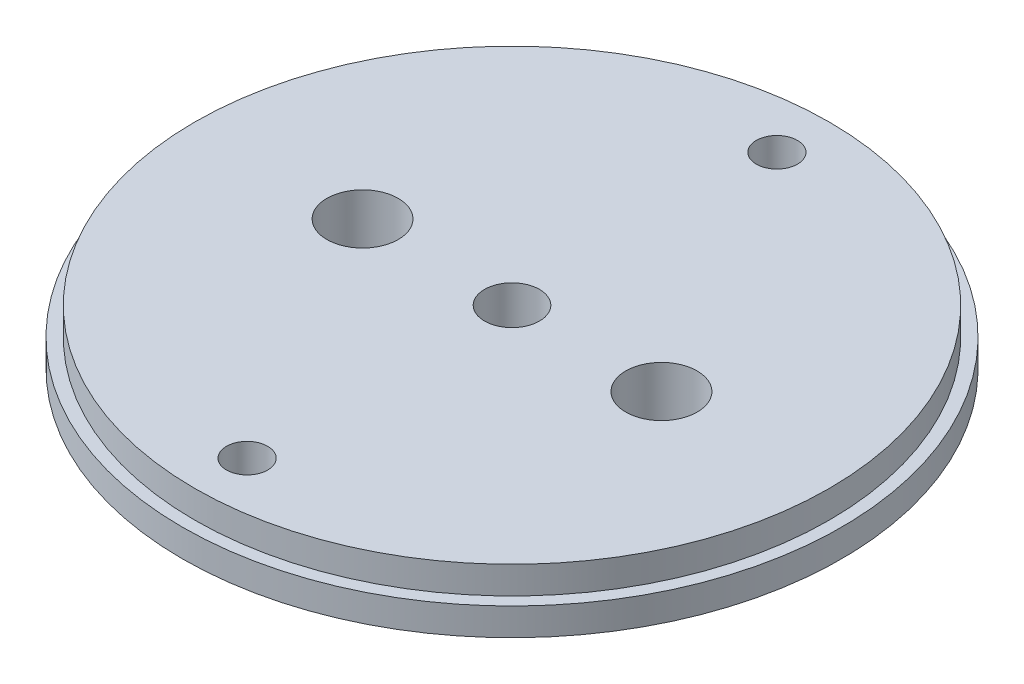
SolidWorks part; units mm, degrees
ref_plane "Front Plane" through (0, 0, 0) normal (0, 0, 1) x (1, 0, 0)
ref_plane "Top Plane" through (0, 0, 0) normal (0, 1, 0) x (1, 0, 0)
ref_plane "Right Plane" through (0, 0, 0) normal (1, 0, 0) x (0, 0, -1)
sketch "Sketch1" plane through (0, 0, 0) normal (0, 1, 0) x (1, 0, 0)
  circle A0 centre (0, 0) radius 73.3425
  circle A1 centre (0, 0) radius 76.1746
  dimension "D1" = 146.685
  dimension "D2" = 152.3492
extrude "Boss-Extrude1" add sketch "Sketch1" along normal blind 6.35 contours A0 | A1 A0 region at (0, 0, 0) region at (-74.0201, 0, 0)
extrude "Boss-Extrude2" add sketch "Sketch1<3>" along normal blind 12.7 contours A0 region at (0, 0, 0)
sketch "Sketch1<3>" plane through (0, 0, 0) normal (0, 1, 0) x (1, 0, 0) same geometry as "Sketch1"
sketch "Sketch3" plane through (0, 0, 0) normal (0, -1, 0) x (1, 0, 0)
  line L0 (34.5453, 0) -> (-34.5453, 0) construction
  line L1 (0, -61.2273) -> (0, 61.2273) construction
  circle A0 centre (0, 0) radius 6.35
  circle A1 centre (-34.5453, 0) radius 8.25
  circle A2 centre (34.5453, 0) radius 8.25
  circle A3 centre (0, 61.2273) radius 4.7625
  circle A4 centre (0, -61.2273) radius 4.7625
  point P6 (0, 0)
  point P14 (0, 0)
  dimension "D1" = 12.7
  dimension "D2" = 16.5001
  dimension "D3" = 9.525
extrude "Cut-Extrude1" cut sketch "Sketch3" against normal through all
sketch "Sketch5" plane through (0, 12.7, 0) normal (0, 1, 0) x (1, 0, 0)
  line L1 (7.8498, 65.9587) -> (-0.1726, 70.3911)
  line L2 (-0.1726, 70.3911) -> (-8.0224, 65.6597)
  line L3 (-8.0224, 65.6597) -> (-7.8498, 56.4959)
  line L4 (-7.8498, 56.4959) -> (0.1726, 52.0635)
  line L5 (0.1726, 52.0635) -> (8.0224, 56.7949)
  line L6 (8.0224, 56.7949) -> (7.8498, 65.9587)
  line L7 (8.6495, -58.1955) -> (1.6991, -52.2207)
  line L8 (1.6991, -52.2207) -> (-6.9503, -55.2525)
  line L9 (-6.9503, -55.2525) -> (-8.6495, -64.2591)
  line L10 (-8.6495, -64.2591) -> (-1.6991, -70.2338)
  line L11 (-1.6991, -70.2338) -> (6.9503, -67.2021)
  line L12 (6.9503, -67.2021) -> (8.6495, -58.1955)
  circle A0 centre (0, 61.2273) radius 7.9375 construction
  circle A1 centre (0, -61.2273) radius 7.9375 construction
  dimension "D1" = 15.875
